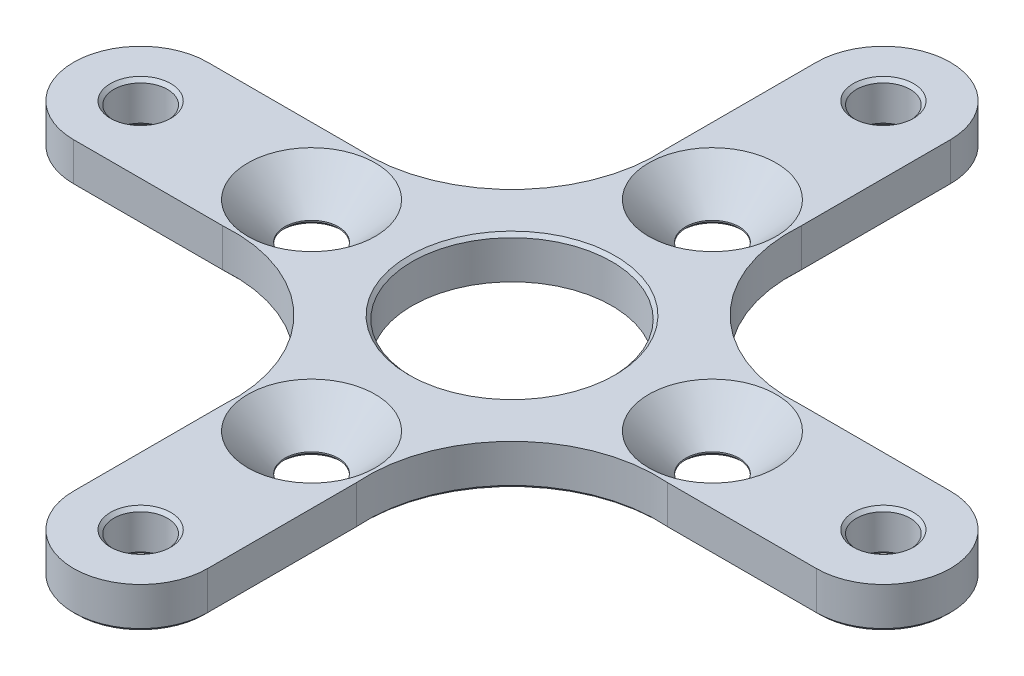
SolidWorks part; units mm, degrees
note: '?' marks a value the reader was unsure of.
other "Sunlight"
material "6061 Alloy"
ref_plane "Front Plane" through (0, 0, 0) normal (0, 0, 1) x (1, 0, 0)
ref_plane "Top Plane" through (0, 0, 0) normal (0, 1, 0) x (1, 0, 0)
ref_plane "Right Plane" through (0, 0, 0) normal (1, 0, 0) x (0, 0, -1)
sketch "Sketch1" plane through (0, 0, 0) normal (0, 1, 0) x (1, 0, 0)
  line L0 (0, 0) -> (0, 27.7) construction
  line L1 (5, 27.7) -> (5, 14.95)
  line L2 (0, 0) -> (11.5, 0) construction
  line L3 (11.5, 0) -> (0, 11.5) construction
  line L4 (0, 0) -> (8.1317, 8.1317) construction
  line L5 (-5, 27.7) -> (-5, 14.95)
  arc A0 (-8.1317, 8.1317) -> (8.1317, 8.1317) centre (0, 0) ccw
  circle A1 centre (0, 0) radius 7.45
  arc A2 (5, 27.7) -> (-5, 27.7) centre (0, 27.7) ccw
  arc A3 (5, 16.5843) -> (8.1317, 8.1317) centre (15.7671, 15.7671) ccw
  circle A4 centre (0, 14.95) radius 2
  circle A5 centre (0, 27.7) radius 2
  arc A6 (-5, 16.5843) -> (-8.1317, 8.1317) centre (-15.7671, 15.7671) cw
  point P8 (0, 12.95)
  point P17 (0, 7.45)
  point P19 (0, 25.7)
  point P20 (0, 16.95)
  point P21 (0, 0)
  point P25 (0, 0)
  dimension "D1" = 23
  dimension "D2" = 14.9
  dimension "D4" = 4
  dimension "D6" = 4
  dimension "D8" = 10.7981
  dimension "D3" = 5
  dimension "D5" = 5.5
  dimension "D7" = 8.75
extrude "Boss-Extrude1" add sketch "Sketch1" along normal blind 3.1 contours L5 A6 A0 A3 L1 A2 A1 A4 A5
ref_axis "Axis1" through (0, 3.1, 0) along (0, -1, 0)?
pattern_circular "CirPattern1" count 4 over 360 about axis through (0, 0, 0) along (0, 1, 0) of bodies 101
combine bodies "Combine1" bodies to combine 104 101 102 103
chamfer "Chamfer3" distance 0.25 angle 45 5 edges at (-25.7, 3.1, 0) (0, 3.1, -25.7) (25.7, 3.1, 0) (0, 3.1, 25.7) (7.45, 3.1, 0)
chamfer "Chamfer4" distance 2.75 angle 45 4 edges at (-12.95, 3.1, 0) (0, 3.1, -12.95) (12.95, 3.1, 0) (0, 3.1, 12.95)
chamfer "Chamfer5" distance 0.25 angle 45 24 edges at (-32.7, 0, 0) (-22.1421, 0, -5) (-8.1317, 0, -8.1317) (-8.1317, 0, 8.1317) (-22.1421, 0, 5) (-25.7, 0, 0) (-12.95, 0, 0) (0, 0, -25.7) (0, 0, -12.95) (8.1317, 0, -8.1317) (5, 0, -22.1421) (25.7, 0, 0) (12.95, 0, 0) (8.1317, 0, 8.1317) (22.1421, 0, 5) (0, 0, 25.7) (0, 0, 12.95) (-5, 0, 22.1421) (-5, 0, -22.1421) (0, 0, -32.7) (22.1421, 0, -5) (32.7, 0, 0) (5, 0, 22.1421) (0, 0, 32.7)
